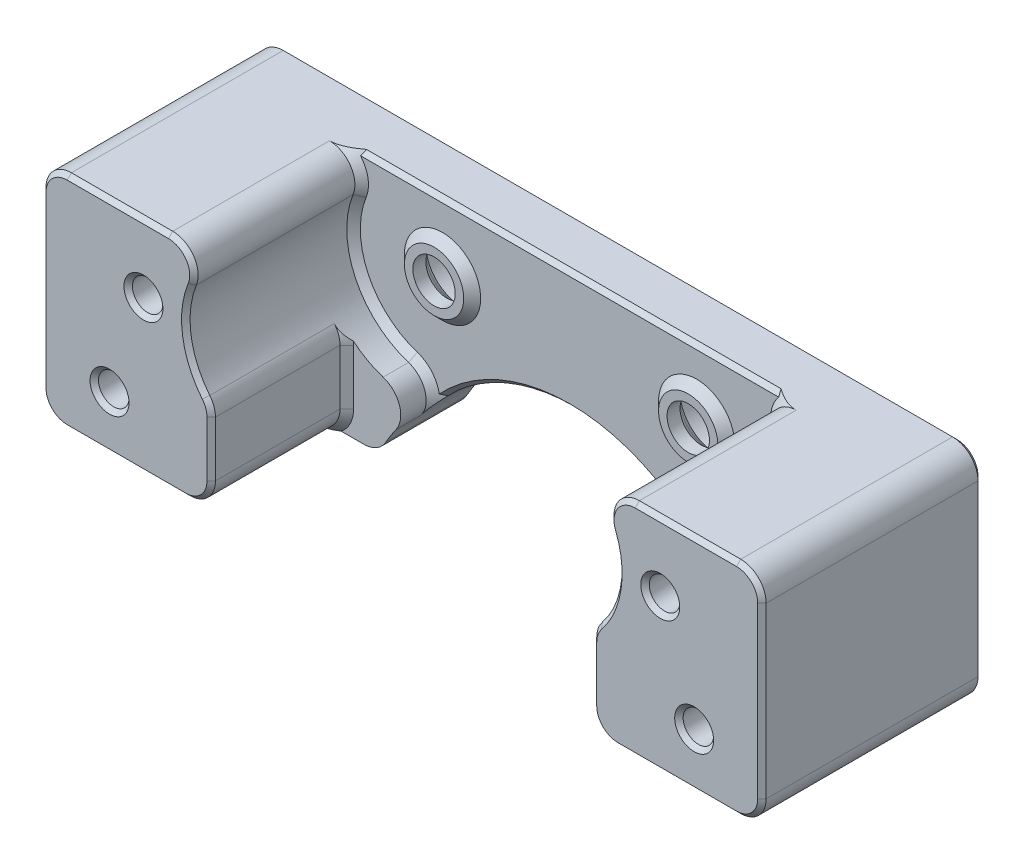
SolidWorks part; units mm, degrees
ref_plane "Front" through (0, 0, 0) normal (0, 0, 1) x (1, 0, 0)
ref_plane "Top" through (0, 0, 0) normal (0, 1, 0) x (1, 0, 0)
ref_plane "Right" through (0, 0, 0) normal (1, 0, 0) x (0, 0, -1)
sketch "Skizze1" plane through (0, 0, 0) normal (0, 0, 1) x (1, 0, 0)
  line L4 (0, 0) -> (0, 53.682) construction
  line L5 (0, 30) -> (-42.5, 30)
  line L6 (-44, 30) -> (44, 30) construction
  line L7 (-42.5, 30) -> (-42.5, 4)
  line L8 (-42.5, 4) -> (-18.6548, 4)
  line L9 (42.5, 30) -> (42.5, 4)
  line L10 (0, 30) -> (42.5, 30)
  line L11 (18.6548, 4) -> (42.5, 4)
  arc A0 (-18.6548, 4) -> (18.6548, 4) centre (0, -4.5) cw
  circle A1 centre (0, -4.5) radius 12.5 construction
  point P13 (0, 4)
  dimension "D3" = 8
  dimension "D1" = 85
  dimension "D2" = 26
extrude "Aufsatz-Linear austragen1" add sketch "Skizze1" along normal blind 10
sketch "Skizze2" plane through (0, 0, 10) normal (0, 0, 1) x (1, 0, 0)
  line L0 (-42.5, 30) -> (-42.5, 4)
  line L1 (-42.5, 4) -> (-22.5, 4)
  line L2 (-42.5, 4) -> (-18.6548, 4) construction
  line L3 (-22.5, 4) -> (-22.5, 14.6515)
  line L4 (42.5, 30) -> (-42.5, 30) construction
  line L5 (-21.8007, 30) -> (-42.5, 30)
  line L6 (0, 0) -> (0, 11.1122) construction
  line L7 (21.8007, 30) -> (42.5, 30)
  line L8 (22.5, 4) -> (22.5, 14.6515)
  line L9 (42.5, 4) -> (22.5, 4)
  line L10 (42.5, 30) -> (42.5, 4)
  arc A0 (-22.5, 14.6515) -> (-21.8007, 30) centre (-15, 22) cw
  circle A1 centre (-15, 22) radius 9 construction
  arc A2 (22.5, 14.6515) -> (21.8007, 30) centre (15, 22) ccw
  dimension "D1" = 1.5
  dimension "D2" = 20
extrude "Aufsatz-Linear austragen2" add sketch "Skizze2" along normal up to surface (16 mm away)
sketch "Skizze3" plane through (0, 0, 10) normal (0, 0, 1) x (1, 0, 0)
  line L0 (0, 0) -> (0, 33.1939) construction
  line L1 (-21.8007, 30) -> (21.8007, 30)
  line L2 (21.8007, 30) -> (-21.8007, 30) construction
  line L3 (-15, 11.5) -> (15, 11.5)
  arc A1 (-22.5, 14.6515) -> (-15, 11.5) centre (-15, 22) ccw
  arc A2 (-22.5, 14.6515) -> (-21.8007, 30) centre (-15, 22) cw
  arc A3 (-21.8007, 30) -> (-22.5, 14.6515) centre (-15, 22) ccw construction
  arc A4 (22.5, 14.6515) -> (21.8007, 30) centre (15, 22) ccw
  arc A5 (22.5, 14.6515) -> (15, 11.5) centre (15, 22) cw
  point P17 (0, 30)
  point P21 (0, 11.5)
extrude "Schnitt-Linear austragen1" cut sketch "Skizze3" against normal offset from surface (3.8 mm away) 1 offset beyond the face yes
sketch "Skizze4" plane through (0, 0, 6.2) normal (0, 0, 1) x (1, 0, 0)
  circle A0 centre (-15, 22) radius 2.5
  circle A1 centre (15, 22) radius 2.5
  dimension "D1" = 5
extrude "Schnitt-Linear austragen2" cut sketch "Skizze4" against normal through all
sketch "Skizze5" plane through (0, 0, 0) normal (0, 0, -1) x (-1, 0, 0)
  circle A0 centre (-15, 22) radius 4.25
  circle A2 centre (15, 22) radius 4.25
  dimension "D1" = 8.5
extrude "Schnitt-Linear austragen3" cut sketch "Skizze5" against normal blind 4.8
chamfer "Fase1" distance 0.87 angle 45 4 edges at (-17.5, 22, 4.8) (-19.25, 22, 4.8) (12.5, 22, 4.8) (10.75, 22, 4.8)
sketch "Skizze6" plane through (0, 0, 6.2) normal (0, 0, 1) x (1, 0, 0)
  circle A0 centre (-15, 22) radius 2.5
  circle A1 centre (-15, 22) radius 3.5
  circle A2 centre (15, 22) radius 2.5
  circle A3 centre (15, 22) radius 3.5
  circle A4 centre (-15, 22) radius 2.5 construction
  dimension "D1" = 7
extrude "Aufsatz-Linear austragen3" add sketch "Skizze6" along normal blind 1
chamfer "Fase2" distance 1 angle 45 2 edges at (15, 25.5, 6.2) (-15, 25.5, 6.2)
sketch "Skizze7" plane through (0, 0, 0) normal (0, 0, -1) x (-1, 0, 0)
  line L0 (-15, 22) -> (-42.5, 22) construction
  line L1 (-42.5, 4) -> (-42.5, 30) construction
  line L2 (0, 30) -> (0, 16) construction
  line L3 (-42.5, 30) -> (42.5, 30) construction
  line L4 (-34.5, 4) -> (-34.5, 30) construction
  line L5 (-18.6548, 4) -> (-42.5, 4) construction
  circle A0 centre (-30.5, 22) radius 1.8
  circle A1 centre (-30.5, 22) radius 3.15
  arc A2 (18.6548, 4) -> (-18.6548, 4) centre (0, -4.5) ccw construction
  circle A3 centre (30.5, 22) radius 1.8
  circle A4 centre (30.5, 22) radius 3.15
  circle A5 centre (-34.5, 10.3737) radius 1.8
  circle A6 centre (-34.5, 10.3737) radius 3.15
  circle A7 centre (34.5, 10.3737) radius 3.15
  circle A8 centre (34.5, 10.3737) radius 1.8
  dimension "D1" = 3.6
  dimension "D2" = 6.3
  dimension "D3" = 8
  dimension "D4" = 12
extrude "Schnitt-Linear austragen4" cut sketch "Skizze7" against normal through all contours A0 | A5 | A3 | A8 region at (30.5, 22, 0) region at (-30.5, 22, 0) region at (34.5, 10.3737, 0) region at (-34.5, 10.3737, 0)
extrude "Schnitt-Linear austragen5" cut sketch "Skizze7<3>" against normal offset from surface (20 mm away) 6 up to face at (32.7, 10.3737, 26)
sketch "Skizze7<3>" plane through (0, 0, 0) normal (0, 0, -1) x (-1, 0, 0) same geometry as "Skizze7"
chamfer "Fase3" distance 0.67 angle 45 8 edges at (-36.3, 10.3737, 20) (-37.65, 10.3737, 20) (-33.65, 22, 20) (-32.3, 22, 20) (27.35, 22, 20) (28.7, 22, 20) (32.7, 10.3737, 20) (31.35, 10.3737, 20)
fillet "Verrundung1" radius 3 14 edges at (22.5, 4, 18) (18.6548, 4, 5) (-18.6548, 4, 5) (-22.5, 4, 18) (-22.5, 14.6515, 18) (22.5, 14.6515, 18) (42.5, 4, 13) (-42.5, 4, 13) (42.5, 30, 13) (-42.5, 30, 13) (-21.8007, 30, 16.1) (21.8007, 30, 16.1) (12.816, 11.5, 8.1) (-12.816, 11.5, 8.1)
chamfer "Fase4" distance 0.8 angle 45 12 edges at (-25.0567, 28.6833, 6.2) (-16.2833, 10.0915, 6.2) (-24.499, 17.5257, 6.2) (16.2833, 10.0915, 6.2) (25.0567, 28.6833, 6.2) (24.499, 17.5257, 6.2) (22.6716, 14.5147, 10) (23.3787, 4.8787, 10) (22.5, 10.2574, 10) (-23.3787, 4.8787, 10) (-22.6716, 14.5147, 10) (-22.5, 10.2574, 10)
chamfer "Fase5" distance 0.5 angle 45 44 edges at (41.6213, 4.8787, 0) (42.5, 17, 0) (41.6213, 29.1213, 0) (0, 30, 0) (-41.6213, 29.1213, 0) (-42.5, 17, 0) (-41.6213, 4.8787, 0) (-29.997, 4, 0) (-18.978, 4.4112, 0) (0, 16, 0) (18.978, 4.4112, 0) (29.997, 4, 0) (-19.25, 22, 0) (10.75, 22, 0) (27.35, 22, 0) (-31.35, 10.3737, 0) (31.35, 10.3737, 0) (-27.35, 22, 0) (22.6716, 14.5147, 26) (25.3819, 20.4295, 26) (25.0567, 28.6833, 26) (33.52, 30, 26) (41.6213, 29.1213, 26) (42.5, 17, 26) (41.6213, 4.8787, 26) (32.5, 4, 26) (23.3787, 4.8787, 26) (22.5, 10.2574, 26) (28.7, 22, 26) (32.7, 10.3737, 26) (-41.6213, 4.8787, 26) (-42.5, 17, 26) (-41.6213, 29.1213, 26) (-33.52, 30, 26) (-25.0567, 28.6833, 26) (-25.3819, 20.4295, 26) (-22.6716, 14.5147, 26) (-22.5, 10.2574, 26) (-23.3787, 4.8787, 26) (-32.5, 4, 26) (-32.3, 22, 26) (-36.3, 10.3737, 26) (0, 16, 6.2) (0, 30, 6.2)
